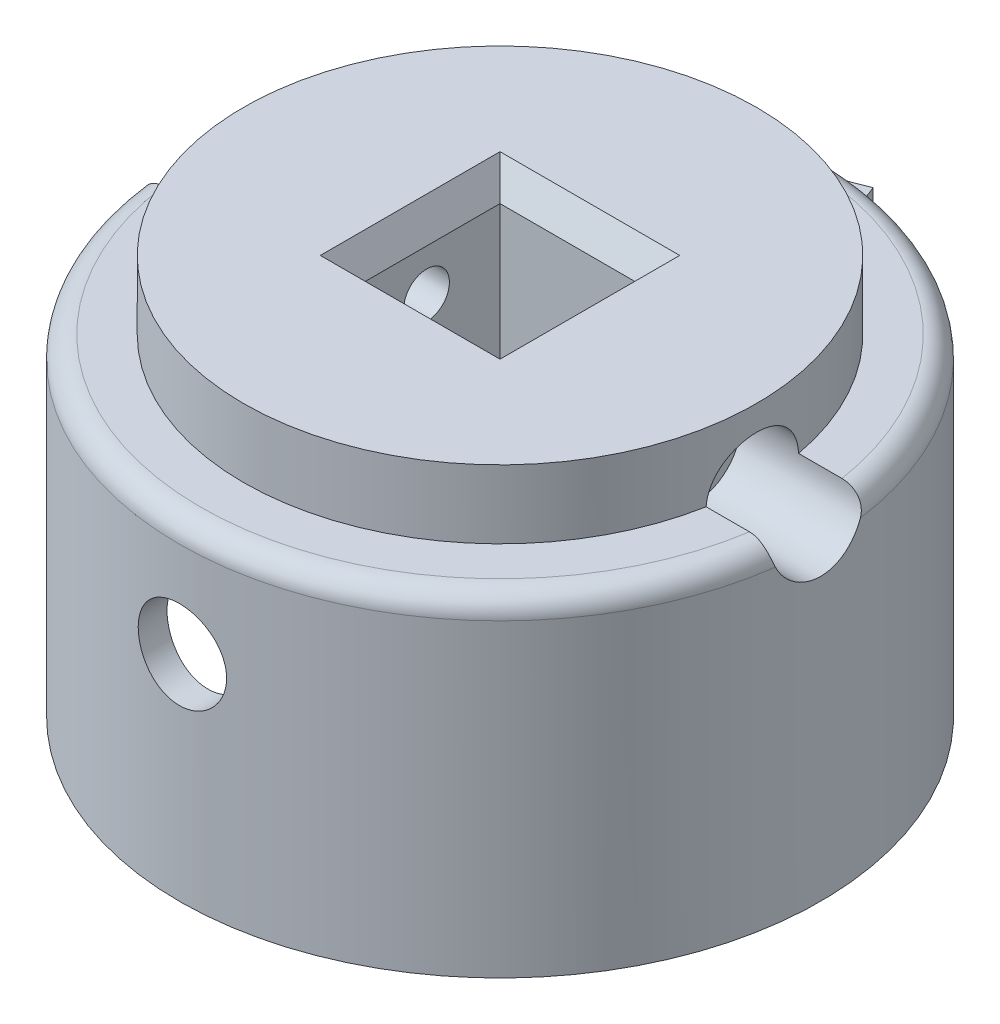
SolidWorks part; units mm, degrees
ref_plane "Спереди" through (0, 0, 0) normal (0, 0, 1) x (1, 0, 0)
ref_plane "Сверху" through (0, 0, 0) normal (0, 1, 0) x (1, 0, 0)
ref_plane "Справа" through (0, 0, 0) normal (1, 0, 0) x (0, 0, -1)
sketch "Sketch1" plane through (0, 0, 0) normal (0, 1, 0) x (1, 0, 0)
  circle A0 centre (0, 0) radius 22.5
  dimension "D1" = 45
extrude "Boss-Extrude1" add sketch "Sketch1" along normal blind 28
sketch "Sketch2" plane through (0, 0, 0) normal (0, -1, 0) x (1, 0, 0)
  line L1 (5.15, 5.15) -> (-5.15, 5.15)
  line L2 (5.15, 5.15) -> (5.15, -5.15)
  line L3 (5.15, -5.15) -> (-5.15, -5.15)
  line L4 (-5.15, 5.15) -> (-5.15, -5.15)
  line L5 (5.15, 5.15) -> (-5.15, -5.15) construction
  line L6 (5.15, -5.15) -> (-5.15, 5.15) construction
  point P0 (0, 0)
  dimension "D1" = 10.3
extrude "Cut-Extrude2" cut sketch "Sketch2" against normal through all
shell "Shell3" thickness 2 removed face at (0, 0, 0)
sketch "Sketch3" plane through (0, 0, 7.15) normal (0, 0, 1) x (1, 0, 0)
  line L0 (0, 26) -> (0, 0) construction
  line L1 (7.15, 26) -> (-7.15, 26) construction
  line L2 (7.15, 0) -> (-7.15, 0) construction
  line L3 (-22.5, 0) -> (22.5, 0) construction
  circle A0 centre (0, 15) radius 3.1
  dimension "D1" = 6.2
  dimension "D2" = 15
extrude "Cut-Extrude3" cut sketch "Sketch3" along normal through all
chamfer "Chamfer1" distance 2 angle 30 4 edges at (-5.15, 28, 0) (0, 28, 5.15) (5.15, 28, 0) (0, 28, -5.15) first distance on face at (-5.15, 14, 0) first distance on face at (0, 14, 5.15) first distance on face at (5.15, 14, 0) first distance on face at (0, 14, -5.15)
sketch "Sketch18" plane through (0, 26, 0) normal (0, -1, 0) x (1, 0, 0)
  line L0 (0, 0) -> (-18.4253, -8.9866) construction
  line L1 (0, 0) -> (-17.385, 10.8633) construction
  line L2 (0, 0) -> (0, -20.5) construction
  line L3 (-15.7289, -7.6715) -> (-18.4253, -8.9866)
  line L4 (-14.8408, 9.2736) -> (-17.385, 10.8633)
  circle A0 centre (0, 0) radius 20.5 construction
  arc A1 (-18.4253, -8.9866) -> (-17.385, 10.8633) centre (0, 0) cw
  arc A2 (-14.8408, 9.2736) -> (-15.7289, -7.6715) centre (0, 0) ccw
  dimension "D1" = 64
  dimension "D2" = 58
  dimension "D3" = 3
extrude "Boss-Extrude8" add sketch "Sketch18" along normal offset from surface (23 mm away) 3 up to face at (0, 0, 20.5)
sketch "Sketch9" plane through (0, 0, 0) normal (0, -1, 0) x (1, 0, 0)
  line L0 (0, -7.15) -> (0, -20.5) construction
  line L2 (2.0571, -22.4058) -> (-16.5967, -15.1921)
  line L3 (-16.5967, -15.1921) -> (-17.6788, -17.9902)
  line L4 (-17.6788, -17.9902) -> (0.975, -25.2038)
  line L5 (0.975, -25.2038) -> (2.0571, -22.4058)
  line L6 (-7.15, -7.15) -> (7.15, -7.15) construction
  line L7 (2.0571, -22.4058) -> (0, -7.15) construction
  circle A0 centre (0, 0) radius 22.5 construction
  circle A1 centre (0, 0) radius 20.5 construction
  dimension "D1" = 20
  dimension "D2" = 3
  dimension "D3" = 7.679
extrude "Boss-Extrude4" add sketch "Sketch9" against normal blind 20
sketch "Sketch11" plane through (0, 0, 0) normal (0, -1, 0) x (1, 0, 0)
  line L0 (2.0571, -22.4058) -> (7.15, -7.15)
  line L1 (7.15, -7.15) -> (-7.15, -7.15)
  line L2 (-7.15, -7.15) -> (-16.5967, -15.1921)
  line L3 (-16.5967, -15.1921) -> (2.0571, -22.4058) construction
  line L4 (-3.78, -20.1485) -> (-10.7596, -17.4494) construction
  arc A0 (2.0571, -22.4058) -> (-16.5967, -15.1921) centre (0, 0) ccw construction
  arc A1 (2.0571, -22.4058) -> (-16.5967, -15.1921) centre (0, 0) cw
  arc A2 (2.0571, -22.4058) -> (-16.5967, -15.1921) centre (0, 0) ccw construction
  point P4 (-7.2698, -18.7989)
extrude "Boss-Extrude6" add sketch "Sketch11" against normal up to surface (26 mm away) up to face at (0, 26, 0)
sketch "Sketch12" plane through (0, 0, 0) normal (0, -1, 0) x (1, 0, 0)
  line L0 (-7.15, -7.15) -> (-15.0727, -13.8947) construction
  line L1 (2.7554, -20.314) -> (7.15, -7.15) construction
  line L2 (3.8359, -17.0772) -> (2.7554, -20.314)
  line L3 (-15.0727, -13.8947) -> (-12.7884, -11.95)
  arc A0 (2.7554, -20.314) -> (-15.0727, -13.8947) centre (0, 0) cw
  arc A1 (-12.7884, -11.95) -> (3.8359, -17.0772) centre (0, 0) ccw
  arc A2 (2.7554, -20.314) -> (-15.0727, -13.8947) centre (0, 0) ccw construction
  dimension "D1" = 3
extrude "Cut-Extrude5" cut sketch "Sketch12" against normal blind 12
sketch "Sketch13" plane through (-8.3519, 0, -21.597) normal (-0.3607, 0, -0.9327) x (-0.9327, 0, 0.3607)
  line L0 (0, 20) -> (0, 0) construction
  line L1 (10, 20) -> (-10, 20) construction
  line L2 (10, 0) -> (-10, 0) construction
  circle A0 centre (0, 10) radius 3.8
  dimension "D1" = 7.6
extrude "Cut-Extrude6" cut sketch "Sketch13" against normal blind 16
sketch "Sketch15" plane through (-8.3519, 0, -21.597) normal (-0.3607, 0, -0.9327) x (-0.9327, 0, 0.3607)
  line L0 (-10, 10) -> (10, 10) construction
  line L1 (-10, 20) -> (-10, 0) construction
  line L2 (10, 20) -> (10, 0) construction
  line L4 (5, 11.5) -> (-5, 11.5)
  line L5 (5, 11.5) -> (5, 8.5)
  line L6 (5, 8.5) -> (-5, 8.5)
  line L7 (-5, 11.5) -> (-5, 8.5)
  line L8 (5, 11.5) -> (-5, 8.5) construction
  line L9 (5, 8.5) -> (-5, 11.5) construction
  point P6 (0, 10)
  dimension "D1" = 10
  dimension "D2" = 3
extrude "Cut-Extrude8" cut sketch "Sketch15" against normal blind 16
sketch "Sketch17" plane through (0, 0, 0) normal (0, -1, 0) x (1, 0, 0)
  line L0 (7.15, 7.15) -> (7.15, -7.15)
  line L1 (7.15, -7.15) -> (3.8359, -17.0772)
  line L2 (7.15, 7.15) -> (-7.15, 7.15)
  line L3 (-7.15, 7.15) -> (-7.15, -7.15)
  line L4 (-7.15, -7.15) -> (-12.7884, -11.95)
  arc A0 (3.8359, -17.0772) -> (-12.7884, -11.95) centre (0, 0) cw
  arc A1 (-12.7884, -11.95) -> (3.8359, -17.0772) centre (0, 0) ccw construction
extrude "Cut-Extrude9" cut sketch "Sketch17" against normal blind 2
sketch "Sketch20" plane through (0, 26, 0) normal (0, -1, 0) x (1, 0, 0)
  line L0 (2.7554, -20.314) -> (7.15, -7.15)
  line L1 (7.15, -7.15) -> (7.15, 7.15)
  line L2 (7.15, 7.15) -> (-7.15, 7.15)
  line L3 (-7.15, 7.15) -> (-7.15, -7.15)
  line L4 (-7.15, -7.15) -> (-15.0727, -13.8947)
  arc A0 (2.7554, -20.314) -> (-15.0727, -13.8947) centre (0, 0) ccw
  arc A1 (2.7554, -20.314) -> (-17.385, 10.8633) centre (0, 0) ccw construction
extrude "Boss-Extrude10" add sketch "Sketch20" along normal blind 7
sketch "Sketch21" plane through (0, 28, 0) normal (0, 1, 0) x (1, 0, 0)
  circle A0 centre (0, 0) radius 18
  dimension "D1" = 36
extrude "Cut-Extrude11" cut sketch "Sketch21" against normal blind 4.8 flip side to cut
sketch "Sketch22" plane through (5.15, 0, 0) normal (-1, 0, 0) x (0, 0, 1)
  line L0 (0, 26) -> (0, 2) construction
  line L1 (5.15, 26) -> (-5.15, 26) construction
  line L2 (-5.15, 2) -> (5.15, 2) construction
  line L3 (-6.3047, 28) -> (6.3047, 28) construction
  circle A0 centre (0, 23) radius 1.6
  point P10 (0, 28)
  dimension "D1" = 3.2
  dimension "D2" = 5
extrude "Cut-Extrude12" cut sketch "Sketch22" against normal through all both and the other way through all
sketch "Sketch24" plane through (5.15, 0, 0) normal (-1, 0, 0) x (0, 0, 1)
  circle A0 centre (0, 23) radius 3.25
  dimension "D1" = 6.5
extrude "Cut-Extrude13" cut sketch "Sketch24" against normal through all from offset 8.5 offset against normal yes
sketch "Sketch25" plane through (-5.15, 0, 0) normal (1, 0, 0) x (0, 0, -1)
  line L0 (-5.15, 26) -> (-5.15, 2) construction
  line L1 (0, 19.75) -> (2.8146, 21.375)
  line L2 (2.8146, 21.375) -> (2.8146, 24.625)
  line L3 (2.8146, 24.625) -> (0, 26.25)
  line L4 (0, 26.25) -> (-2.8146, 24.625)
  line L5 (-2.8146, 24.625) -> (-2.8146, 21.375)
  line L6 (-2.8146, 21.375) -> (0, 19.75)
  circle A0 centre (0, 23) radius 3.25 construction
  dimension "D1" = 6.5
extrude "Cut-Extrude14" cut sketch "Sketch25" against normal through all from offset 8.5 offset against normal yes
fillet "Fillet1" radius 1.5 2 edges at (-0.2166, 23.2, 22.499) (-0.2166, 23.2, -22.499)
